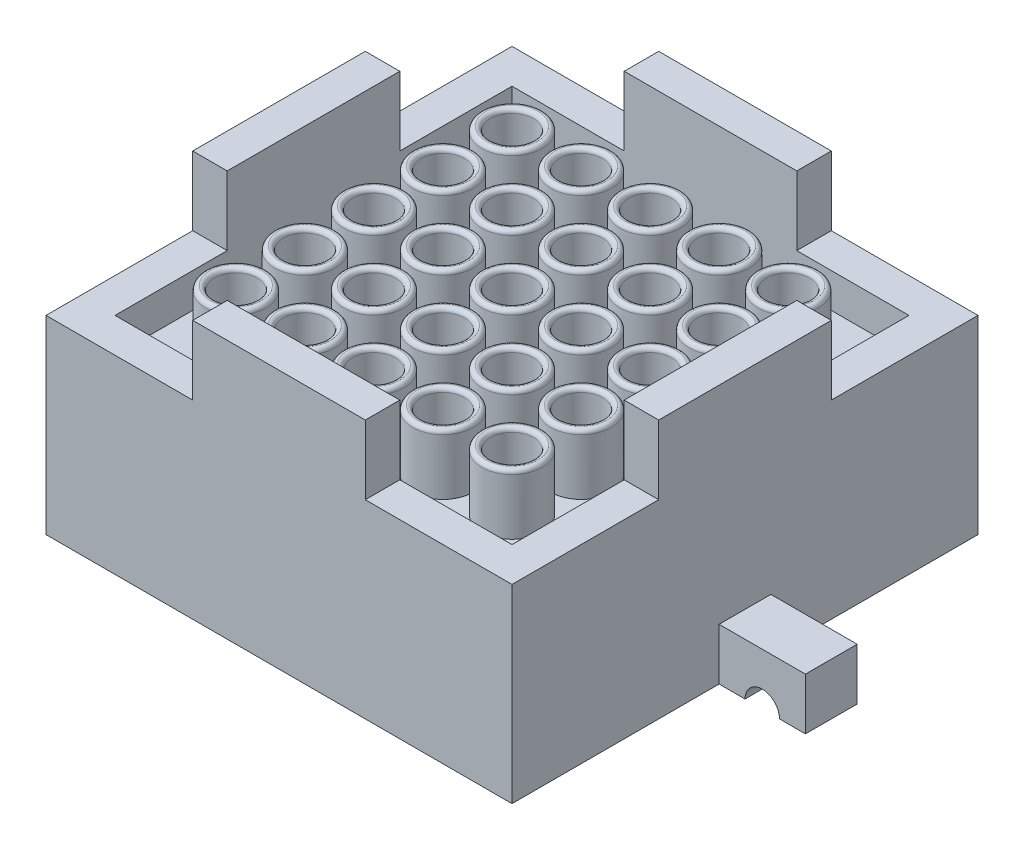
SolidWorks part; units mm, degrees
ref_plane "Front Plane" through (0, 0, 0) normal (0, 0, 1) x (1, 0, 0)
ref_plane "Top Plane" through (0, 0, 0) normal (0, 1, 0) x (1, 0, 0)
ref_plane "Right Plane" through (0, 0, 0) normal (1, 0, 0) x (0, 0, -1)
sketch "Sketch1" plane through (0, 0, 0) normal (0, 1, 0) x (1, 0, 0)
  line L0 (-13.5, 13.5) -> (13.5, 13.5)
  line L1 (-11.5, -11.5) -> (11.5, -11.5)
  line L2 (-11.5, -11.5) -> (-11.5, 11.5)
  line L3 (-11.5, 11.5) -> (11.5, 11.5)
  line L4 (11.5, -11.5) -> (11.5, 11.5)
  line L5 (-11.5, -11.5) -> (11.5, 11.5) construction
  line L6 (-11.5, 11.5) -> (11.5, -11.5) construction
  line L7 (13.5, -13.5) -> (13.5, 13.5)
  line L8 (-13.5, -13.5) -> (13.5, -13.5)
  line L9 (-13.5, -13.5) -> (-13.5, 13.5)
  point P0 (0, 0)
  dimension "D1" = 23
  dimension "D2" = 2
extrude "Boss-Extrude1" add sketch "Sketch1" along normal blind 2
sketch "Sketch2" plane through (0, 0, 0) normal (0, -1, 0) x (1, 0, 0)
  line L1 (-13.5, 13.5) -> (13.5, 13.5)
  line L2 (-13.5, 13.5) -> (-13.5, -13.5)
  line L3 (-13.5, -13.5) -> (13.5, -13.5)
  line L4 (13.5, 13.5) -> (13.5, -13.5)
  line L5 (-13.5, 13.5) -> (13.5, -13.5) construction
  line L6 (-13.5, -13.5) -> (13.5, 13.5) construction
  point P0 (0, 0)
extrude "Boss-Extrude2" add sketch "Sketch2" along normal blind 2
sketch "Sketch3" plane through (0, -2, 0) normal (0, -1, 0) x (1, 0, 0)
  line L0 (-11.5, 11.5) -> (11.5, 11.5)
  line L1 (-13.5, -13.5) -> (13.5, -13.5)
  line L2 (-13.5, -13.5) -> (-13.5, 13.5)
  line L3 (-13.5, 13.5) -> (13.5, 13.5)
  line L4 (13.5, -13.5) -> (13.5, 13.5)
  line L5 (-13.5, -13.5) -> (13.5, 13.5) construction
  line L6 (-13.5, 13.5) -> (13.5, -13.5) construction
  line L7 (11.5, -11.5) -> (11.5, 11.5)
  line L8 (-11.5, -11.5) -> (11.5, -11.5)
  line L9 (-11.5, -11.5) -> (-11.5, 11.5)
  point P0 (0, 0)
  dimension "D1" = 2
extrude "Boss-Extrude3" add sketch "Sketch3" along normal blind 5
sketch "Sketch6" plane through (0, 0, 0) normal (0, 1, 0) x (1, 0, 0)
  line L0 (11.5, -11.5) -> (11.5, 11.5) construction
  line L1 (11.5, 11.5) -> (-11.5, 11.5) construction
  circle A0 centre (8, 8) radius 1.75
  dimension "D2" = 3.5
  dimension "D1" = 3.5
  dimension "D3" = 3.5
extrude "Boss-Extrude5" add sketch "Sketch6" along normal blind 3.5
sketch "Sketch7" plane through (0, 3.5, 0) normal (0, 1, 0) x (1, 0, 0)
  circle A0 centre (8, 8) radius 1.25
  circle A1 centre (8, 8) radius 1.75 construction
  dimension "D1" = 0.5
extrude "Cut-Extrude2" cut sketch "Sketch7" against normal up to next
fillet "Fillet1" radius 0.25 2 edges at (8, 3.5, -6.25) (8, 3.5, -6.75)
pattern_linear "LPattern3" count 5 spacing 4 along (0, 0, 1) count 5 spacing 4 along (-1, 0, 0) of "Boss-Extrude5", "Cut-Extrude2", "Fillet1"
sketch "Sketch11" plane through (0, -2, 0) normal (0, -1, 0) x (1, 0, 0)
  line L0 (11.5, 11.5) -> (-11.5, 11.5) construction
  line L1 (-11.5, 11.5) -> (-11.5, -11.5) construction
  circle A0 centre (-9.9, 9.9) radius 0.75
  dimension "D1" = 1.5
  dimension "D3" = 1.6
  dimension "D2" = 1.6
extrude "Boss-Extrude8" add sketch "Sketch11" along normal up to surface (5 mm away) up to face at (0, -7, 0)
pattern_linear "LPattern2" count 6 spacing 4 along (1, 0, 0) count 6 spacing 4 along (0, 0, -1) of "Boss-Extrude8"
sketch "Sketch8" plane through (0, -7, 0) normal (0, -1, 0) x (1, 0, 0)
  line L1 (-13.5, -13.5) -> (13.5, -13.5)
  line L2 (-13.5, -13.5) -> (-13.5, 13.5)
  line L3 (-13.5, 13.5) -> (13.5, 13.5)
  line L4 (13.5, -13.5) -> (13.5, 13.5)
  line L5 (-13.5, -13.5) -> (13.5, 13.5) construction
  line L6 (-13.5, 13.5) -> (13.5, -13.5) construction
  point P0 (0, 0)
extrude "Boss-Extrude6" add sketch "Sketch8" along normal blind 2
sketch "Sketch9" plane through (0, -9, 0) normal (0, -1, 0) x (1, 0, 0)
  circle A0 centre (0, 0) radius 4.25
  dimension "D1" = 8.5
extrude "Cut-Extrude3" cut sketch "Sketch9" against normal blind 7
sketch "Sketch10" plane through (0, 2, 0) normal (0, 1, 0) x (1, 0, 0)
  line L0 (-13.5, 0) -> (-11.5, 0) construction
  line L1 (-13.5, 13.5) -> (-13.5, -13.5) construction
  line L2 (-11.5, 11.5) -> (-11.5, -11.5) construction
  line L4 (-11.5, 5) -> (-13.5, 5)
  line L5 (-11.5, 5) -> (-11.5, -5)
  line L6 (-11.5, -5) -> (-13.5, -5)
  line L7 (-13.5, 5) -> (-13.5, -5)
  line L8 (-11.5, 5) -> (-13.5, -5) construction
  line L9 (-11.5, -5) -> (-13.5, 5) construction
  point P6 (-12.5, 0)
  dimension "D1" = 10
extrude "Boss-Extrude7" add sketch "Sketch10" along normal blind 4
pattern_circular "CirPattern2" count 4 over 360 about axis through (0, -7.001, 0) along (0, 1, 0) of "Boss-Extrude7"
sketch "Sketch12" plane through (-13.5, 0, 0) normal (-1, 0, 0) x (0, 0, 1)
  line L0 (13.5, -9) -> (-13.5, -9) construction
  line L1 (1.5, -6) -> (-1.5, -6)
  line L2 (1.5, -6) -> (1.5, -9)
  line L3 (1.5, -9) -> (-1.5, -9)
  line L4 (-1.5, -6) -> (-1.5, -9)
  line L5 (1.5, -6) -> (-1.5, -9) construction
  line L6 (1.5, -9) -> (-1.5, -6) construction
  line L7 (0, 0) -> (0, -9) construction
  point P0 (0, -7.5)
  dimension "D1" = 3
extrude "Boss-Extrude9" add sketch "Sketch12" along normal blind 5
pattern_circular "CirPattern1" count 2 over 360 about axis through (0, -7.001, 0) along (0, 1, 0) of "Boss-Extrude9"
sketch "Sketch13" plane through (0, 0, 1.5) normal (0, 0, 1) x (1, 0, 0)
  line L0 (18.5, -9) -> (13.5, -9) construction
  line L1 (15, -9) -> (17, -9)
  line L2 (-18.5, -9) -> (-13.5, -9) construction
  line L3 (-17, -9) -> (-15, -9)
  arc A0 (17, -9) -> (15, -9) centre (16, -9) ccw
  arc A1 (-15, -9) -> (-17, -9) centre (-16, -9) ccw
  dimension "D1" = 1
  dimension "D2" = 1
extrude "Cut-Extrude4" cut sketch "Sketch13" against normal up to next
equation "\"D3@Sketch6\"=\"D1@Sketch6\""
equation "\"D3@Sketch11\"=\"D2@Sketch11\""
equation "\"D2@Sketch13\"=\"D1@Sketch13\""
